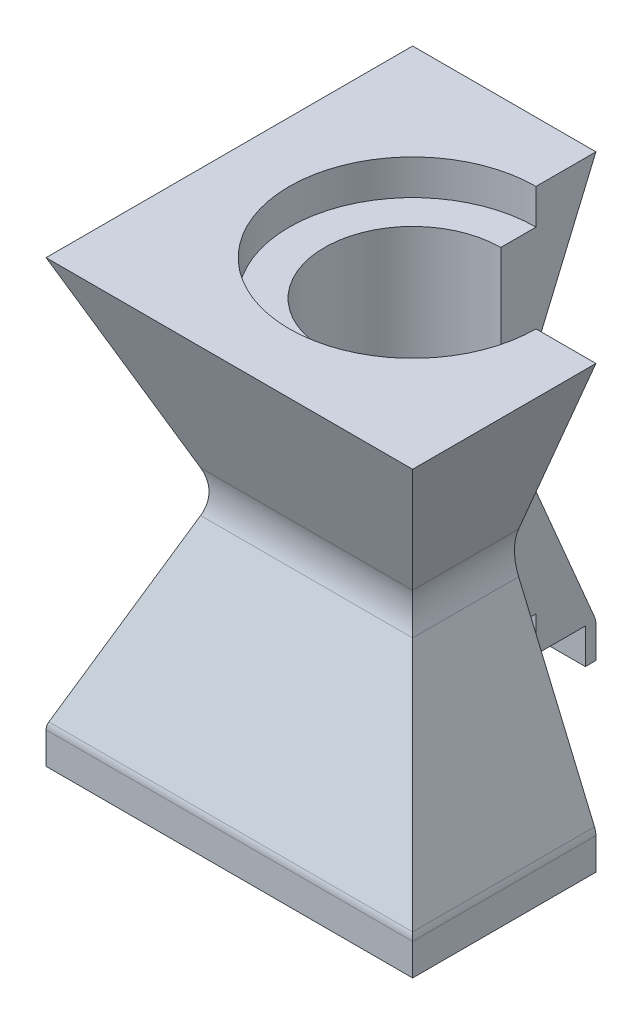
SolidWorks part; units mm, degrees
material "Cast Stainless Steel"
ref_plane "Front Plane" through (0, 0, 0) normal (0, 0, 1) x (1, 0, 0)
ref_plane "Top Plane" through (0, 0, 0) normal (0, 1, 0) x (1, 0, 0)
ref_plane "Right Plane" through (0, 0, 0) normal (1, 0, 0) x (0, 0, -1)
sketch "Sketch1" plane through (0, 0, 0) normal (0, 1, 0) x (1, 0, 0)
  line L1 (-52, 52) -> (52, 52)
  line L2 (-52, 52) -> (-52, -52)
  line L3 (-52, -52) -> (52, -52)
  line L4 (52, 52) -> (52, -52)
  line L5 (-52, 52) -> (52, -52) construction
  line L6 (-52, -52) -> (52, 52) construction
  point P0 (0, 0)
  dimension "D1" = 104
  dimension "D2" = 104
extrude "Boss-Extrude1" add sketch "Sketch1" along normal blind 57.5 draft 23
mirror "Mirror1" about plane through (0, 57.5, 0) normal (0, 1, 0) of bodies 101
sketch "Sketch2" plane through (0, 0, 0) normal (0, -1, 0) x (-1, 0, 0)
  circle A0 centre (0, 0) radius 25
  dimension "D1" = 50
extrude "Cut-Extrude1" cut sketch "Sketch2" against normal through all
sketch "Sketch7" plane through (0, 115, 0) normal (0, 1, 0) x (1, 0, 0)
  circle A0 centre (0, 0) radius 35
  dimension "D1" = 70
extrude "Cut-Extrude6" cut sketch "Sketch7" against normal blind 10
sketch "Sketch8" plane through (0, 0, 0) normal (0, -1, 0) x (1, 0, 0)
  circle A0 centre (0, 0) radius 35
  dimension "D1" = 70
extrude "Cut-Extrude7" cut sketch "Sketch8" against normal blind 10
sketch "Sketch9" plane through (0, 0, 0) normal (0, -1, 0) x (-1, 0, 0)
  line L1 (0, 0) -> (-52, 0)
  line L2 (0, 0) -> (0, 52)
  line L3 (0, 52) -> (-52, 52)
  line L4 (-52, 0) -> (-52, 52)
extrude "Cut-Extrude8" cut sketch "Sketch9" against normal through all
fillet "Fillet5" radius 15 4 edges at (27.5927, 57.5, 13.7963) (-13.7963, 57.5, -27.5927) (-27.5927, 57.5, 0) (0, 57.5, 27.5927)
sketch "Sketch10" plane through (0, 0, 0) normal (0, -1, 0) x (1, 0, 0)
  line L0 (52, 0) -> (35, 0) construction
  line L1 (0, -49) -> (0, -52)
  line L2 (49, 0) -> (52, 0)
  line L3 (52, 0) -> (52, 52)
  line L4 (52, 52) -> (-52, 52)
  line L5 (-52, 52) -> (-52, -52)
  line L6 (-52, -52) -> (0, -52)
  line L12 (-49, -49) -> (-3, -49)
  line L13 (-3, -49) -> (-3, -37.8814)
  line L14 (37.8814, 3) -> (49, 3)
  line L15 (49, 3) -> (49, 49)
  line L16 (49, 49) -> (-49, 49)
  line L17 (-49, 49) -> (-49, -49)
  line L18 (-49, -49) -> (0, -49)
  line L21 (49, 0) -> (49, 49)
  line L22 (49, 49) -> (-49, 49)
  line L23 (-49, 49) -> (-49, -49)
  arc A2 (37.8814, 3) -> (-3, -37.8814) centre (0, 0) ccw
  dimension "D1" = 3
extrude "Boss-Extrude2" add sketch "Sketch10" along normal blind 10
sketch "Sketch11" plane through (0, 0, 0) normal (0, -1, 0) x (-1, 0, 0)
  line L0 (0, 0) -> (52, -52)
  line L1 (40.6586, -40.6586) -> (30.052, -30.052) construction
  line L2 (38.5373, -42.78) -> (27.9307, -32.1734)
  line L3 (42.78, -38.5373) -> (32.1734, -27.9307)
  line L4 (-40.6586, -40.6586) -> (-30.052, -30.052) construction
  line L5 (-42.78, -38.5373) -> (-32.1734, -27.9307)
  line L6 (-38.5373, -42.78) -> (-27.9307, -32.1734)
  line L10 (40.6586, 40.6586) -> (30.052, 30.052) construction
  line L11 (42.78, 38.5373) -> (32.1734, 27.9307)
  line L12 (38.5373, 42.78) -> (27.9307, 32.1734)
  line L16 (-40.6586, 40.6586) -> (-30.052, 30.052) construction
  line L17 (-38.5373, 42.78) -> (-27.9307, 32.1734)
  line L18 (-42.78, 38.5373) -> (-32.1734, 27.9307)
  line L19 (-40.6586, 40.6586) -> (-30.052, 30.052) construction
  line L20 (-38.5373, 42.78) -> (-27.9307, 32.1734)
  line L21 (-42.78, 38.5373) -> (-32.1734, 27.9307)
  circle A0 centre (0, 0) radius 50
  arc A1 (38.5373, -42.78) -> (42.78, -38.5373) centre (40.6586, -40.6586) ccw
  arc A2 (32.1734, -27.9307) -> (27.9307, -32.1734) centre (30.052, -30.052) ccw
  arc A3 (-42.78, -38.5373) -> (-38.5373, -42.78) centre (-40.6586, -40.6586) ccw
  arc A4 (-27.9307, -32.1734) -> (-32.1734, -27.9307) centre (-30.052, -30.052) ccw
  arc A7 (42.78, 38.5373) -> (38.5373, 42.78) centre (40.6586, 40.6586) ccw
  arc A8 (27.9307, 32.1734) -> (32.1734, 27.9307) centre (30.052, 30.052) ccw
  arc A13 (-38.5373, 42.78) -> (-42.78, 38.5373) centre (-40.6586, 40.6586) ccw
  arc A14 (-32.1734, 27.9307) -> (-27.9307, 32.1734) centre (-30.052, 30.052) ccw
  point P7 (35.3553, -35.3553)
  point P14 (-35.3553, 35.3553)
  point P17 (-35.3553, -35.3553)
  point P22 (44.7555, 46.1721)
  point P31 (35.3553, 35.3553)
  point P36 (0, 0)
  point P43 (-35.3553, 35.3553)
  point P50 (-35.3553, 35.3553)
  dimension "D1" = 100
  dimension "D3" = 3
  dimension "D2" = 15
  dimension "D4" = 4
extrude "Cut-Extrude9" cut sketch "Sketch11" against normal blind 10 contours L2 A2 L3 A1 | L6 A4 L5 A3 | L11 A8 L12 A7
fillet "Fillet6" radius 5 4 edges at (-26, 0, -52) (-52, 0, 0) (0, 0, 52) (52, 0, 26)
equation "\"A\"= 115mm"
equation "\"B\"= 104mm"
equation "\"C\"= 23mm"
equation "\"D1@Sketch1\"=\"B\""
equation "\"D2@Sketch1\"=\"B\""
equation "\"D1@Boss-Extrude1\"=\"A\"/2"
equation "\"D3@Boss-Extrude1\"=\"C\""
